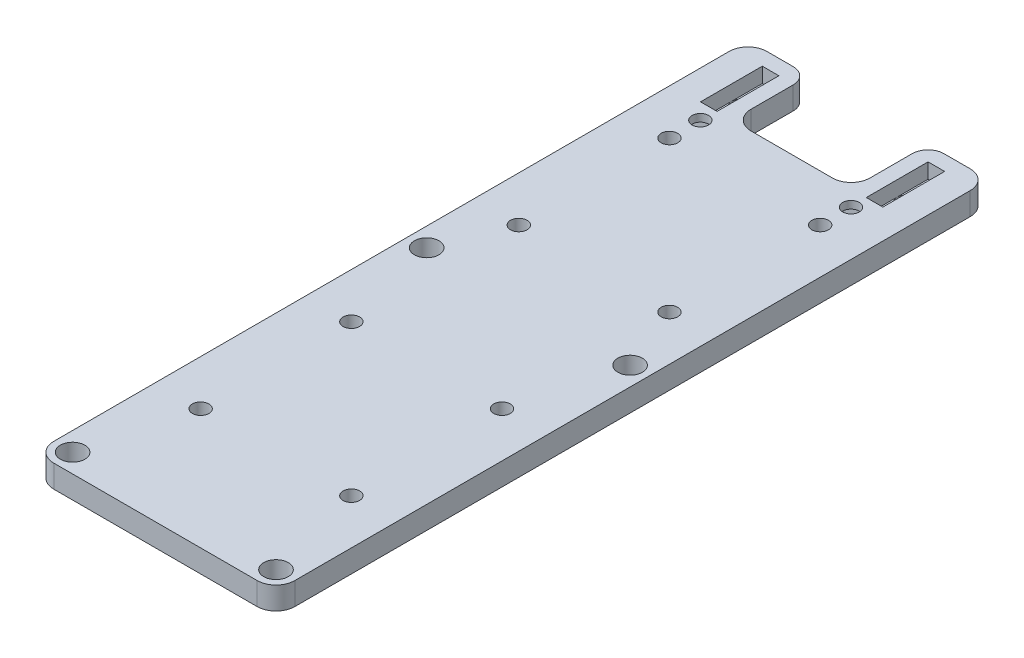
SolidWorks part; units mm, degrees
ref_plane "Front Plane" through (0, 0, 0) normal (0, 0, 1) x (1, 0, 0)
ref_plane "Top Plane" through (0, 0, 0) normal (0, 1, 0) x (1, 0, 0)
ref_plane "Right Plane" through (0, 0, 0) normal (1, 0, 0) x (0, 0, -1)
sketch "Sketch1" plane through (0, 0, 0) normal (0, 1, 0) x (1, 0, 0)
  line L0 (0, 42.225) -> (0, -42.225) construction
  line L1 (16, 42.225) -> (-16, 42.225)
  line L2 (16, 42.225) -> (16, -42.225)
  line L3 (16, -42.225) -> (-16, -42.225)
  line L4 (-16, 42.225) -> (-16, -42.225)
  line L5 (16, 42.225) -> (-16, -42.225) construction
  line L6 (16, -42.225) -> (-16, 42.225) construction
  line L12 (-12.1, 50.425) -> (-12.1, 52.425) construction
  line L17 (-11, 52.425) -> (-11, 42.225) construction
  line L18 (-7.9, 42.225) -> (-14.1, 42.225)
  line L20 (-10, 36) -> (10, 36)
  line L21 (-10, 36) -> (-10, 16)
  line L22 (-10, 16) -> (10, 16)
  line L23 (10, 36) -> (10, 16)
  line L24 (-10, 36) -> (10, 16) construction
  line L25 (-10, 16) -> (10, 36) construction
  line L26 (-14.5, 10.775) -> (14.5, 10.775)
  line L27 (-14.5, 10.775) -> (-14.5, 41.225)
  line L28 (-14.5, 41.225) -> (14.5, 41.225)
  line L29 (14.5, 10.775) -> (14.5, 41.225)
  line L30 (-14.5, 10.775) -> (14.5, 41.225) construction
  line L31 (-14.5, 41.225) -> (14.5, 10.775) construction
  line L32 (-10, -6.225) -> (10, -6.225)
  line L33 (-10, -6.225) -> (-10, -26.225)
  line L34 (-10, -26.225) -> (10, -26.225)
  line L35 (10, -6.225) -> (10, -26.225)
  line L36 (-10, -6.225) -> (10, -26.225) construction
  line L37 (-10, -26.225) -> (10, -6.225) construction
  line L38 (-15.75, -36.225) -> (15.75, -36.225)
  line L39 (-15.75, -36.225) -> (-15.75, 3.775)
  line L40 (-15.75, 3.775) -> (15.75, 3.775)
  line L41 (15.75, -36.225) -> (15.75, 3.775)
  line L42 (-15.75, -36.225) -> (15.75, 3.775) construction
  line L43 (-15.75, 3.775) -> (15.75, -36.225) construction
  line L48 (-7.9, 42.225) -> (-7.9, 52.425)
  line L49 (-7.9, 52.425) -> (-14.1, 52.425)
  line L59 (-14.1, 42.225) -> (-14.1, 52.425)
  line L63 (-12.1, 50.425) -> (-9.9, 50.425)
  line L64 (-12.1, 50.425) -> (-12.1, 42.225)
  line L65 (-12.1, 42.225) -> (-9.9, 42.225)
  line L66 (-9.9, 50.425) -> (-9.9, 42.225)
  line L67 (-12.1, 50.425) -> (-9.9, 42.225) construction
  line L68 (-12.1, 42.225) -> (-9.9, 50.425) construction
  line L69 (-12.1, 50.425) -> (-14.1, 50.425) construction
  line L74 (7.9, 42.225) -> (14.1, 42.225)
  line L75 (14.1, 42.225) -> (14.1, 52.425)
  line L76 (7.9, 52.425) -> (14.1, 52.425)
  line L77 (7.9, 42.225) -> (7.9, 52.425)
  line L78 (12.1, 50.425) -> (9.9, 50.425)
  line L79 (12.1, 50.425) -> (12.1, 42.225)
  line L80 (12.1, 42.225) -> (9.9, 42.225)
  line L81 (9.9, 50.425) -> (9.9, 42.225)
  line L82 (-14.5, 10.775) -> (-14.5, 3.775) construction
  line L83 (-14.5, 7.275) -> (16, 7.275) construction
  line L89 (-13.5, -37.225) -> (-16, -37.225) construction
  line L94 (-14.1, 52.425) -> (-16, 52.425)
  line L95 (-14.1, 52.425) -> (-14.1, 42.225)
  line L96 (-14.1, 42.225) -> (-16, 42.225)
  line L97 (-16, 52.425) -> (-16, 42.225)
  line L98 (14.1, 52.425) -> (16, 52.425)
  line L99 (14.1, 52.425) -> (14.1, 42.225)
  line L100 (14.1, 42.225) -> (16, 42.225)
  line L101 (16, 52.425) -> (16, 42.225)
  circle A3 centre (-10, 36) radius 1.1
  circle A4 centre (10, 36) radius 1.1
  circle A5 centre (10, 16) radius 1.1
  circle A6 centre (-10, 16) radius 1.1
  circle A7 centre (-10, -6.225) radius 1.1
  circle A8 centre (10, -6.225) radius 1.1
  circle A9 centre (10, -26.225) radius 1.1
  circle A10 centre (-10, -26.225) radius 1.1
  circle A37 centre (-13.5, 7.275) radius 2.5
  circle A38 centre (-13.5, 7.275) radius 1.625
  circle A39 centre (13.5, 7.275) radius 1.625
  circle A40 centre (-13.5, -39.725) radius 2.5
  circle A41 centre (-13.5, -39.725) radius 1.625
  circle A42 centre (13.5, -39.725) radius 1.625
  point P0 (0, 0)
  point P8 (0, 0)
  point P16 (0, 26)
  point P26 (0, 26)
  point P31 (0, -16.225)
  point P36 (0, -16.225)
  point P61 (-11, 46.325)
  dimension "D3" = 2
  dimension "D17" = 2.2
  dimension "D22" = 5
  dimension "D23" = 3.25
  dimension "D8" = 32
  dimension "D9" = 22
  dimension "D10" = 20
  dimension "D11" = 29
  dimension "D12" = 30.45
  dimension "D13" = 40
  dimension "D14" = 31.5
  dimension "D15" = 1
  dimension "D16" = 7
  dimension "D18" = 2.2
  dimension "D20" = 8.2
  dimension "D24" = 1
extrude "Boss-Extrude1" add sketch "Sketch1" along normal blind 2 contours L63 L66 L1 L48 L49 L59 L18 L64 | L81 L78 L79 L1 L75 L76 L77 | L94 L97 L1 L59 | L101 L98 L75 L1 | L1 L4 L3 L2 | A4 | A3 | A7 | A8 | A9 | A10 | A5 | A6 | A39 | A38 | A41 | A42 region at (15.05, 0, -47.325) region at (13.1, 0, -42.3444) region at (-8.9, 0, -42.3444) region at (-15.05, 0, -47.325)
sketch "Sketch2" plane through (0, 0, 0) normal (0, -1, 0) x (1, 0, 0)
  line L0 (-12.1, -42.225) -> (-9.9, -50.425) construction
  line L1 (12.1, -42.225) -> (9.9, -50.425) construction
  line L4 (12.1, -42.225) -> (9.9, -42.225)
  line L5 (12.1, -50.425) -> (12.1, -42.225)
  line L6 (9.9, -50.425) -> (12.1, -50.425)
  line L7 (9.9, -42.225) -> (9.9, -50.425)
  line L8 (12.1, -42.225) -> (9.9, -42.225)
  line L9 (12.1, -50.425) -> (12.1, -42.225)
  line L10 (9.9, -50.425) -> (12.1, -50.425)
  line L11 (9.9, -42.225) -> (9.9, -50.425)
  line L12 (-9.9, -42.225) -> (-12.1, -42.225)
  line L13 (-9.9, -50.425) -> (-9.9, -42.225)
  line L14 (-12.1, -50.425) -> (-9.9, -50.425)
  line L15 (-12.1, -42.225) -> (-12.1, -50.425)
  line L16 (-9.9, -42.225) -> (-12.1, -42.225)
  line L17 (-9.9, -50.425) -> (-9.9, -42.225)
  line L18 (-12.1, -50.425) -> (-9.9, -50.425)
  line L19 (-12.1, -42.225) -> (-12.1, -50.425)
  circle A0 centre (-11, -46.325) radius 1.1
  circle A1 centre (11, -46.325) radius 1.1
  dimension "D1" = 0
  dimension "D2" = 0
extrude "Boss-Extrude2" add sketch "Sketch2" against normal offset from surface (1 mm away) 1 contours A0 L19 | A0 L17 | A1 L9 | A1 L11 region at (11, 0, -43.8523) region at (11, 0, -48.7977) region at (-11, 0, -43.8523) region at (-11, 0, -48.7977) up to face at (11, 2, -46.325)
fillet "Fillet1" radius 2.5 6 edges at (7.9, 1, -42.225) (-7.9, 1, -42.225) (-16, 1, -52.425) (16, 1, -52.425) (-16, 1, 42.225) (16, 1, 42.225)
fillet "Fillet2" radius 2.1 2 edges at (-7.9, 1, -52.425) (7.9, 1, -52.425)
sketch "Sketch3" plane through (0, 2, 0) normal (0, 1, 0) x (1, 0, 0)
  line L6 (12.1, 42.225) -> (12.1, 50.425)
  line L7 (9.9, 42.225) -> (12.1, 42.225)
  line L8 (-10, 52.425) -> (-13.5, 52.425)
  line L9 (-16, 49.925) -> (-16, -39.725)
  line L10 (-13.5, -42.225) -> (13.5, -42.225)
  line L11 (16, -39.725) -> (16, 49.925)
  line L12 (13.5, 52.425) -> (10, 52.425)
  line L13 (7.9, 50.325) -> (7.9, 44.725)
  line L14 (5.4, 42.225) -> (-5.4, 42.225)
  line L15 (-7.9, 44.725) -> (-7.9, 50.325)
  line L16 (-10, 52.425) -> (-13.5, 52.425)
  line L17 (-16, 49.925) -> (-16, -39.725)
  line L18 (-13.5, -42.225) -> (13.5, -42.225)
  line L19 (16, -39.725) -> (16, 49.925)
  line L20 (13.5, 52.425) -> (10, 52.425)
  line L21 (7.9, 50.325) -> (7.9, 44.725)
  line L22 (5.4, 42.225) -> (-5.4, 42.225)
  line L23 (-7.9, 44.725) -> (-7.9, 50.325)
  line L24 (9.9, 50.425) -> (9.9, 42.225)
  line L25 (12.1, 50.425) -> (9.9, 50.425)
  line L26 (12.1, 42.225) -> (12.1, 50.425)
  line L27 (9.9, 42.225) -> (12.1, 42.225)
  line L28 (9.9, 50.425) -> (9.9, 42.225)
  line L29 (12.1, 50.425) -> (9.9, 50.425)
  line L30 (-9.9, 42.225) -> (-9.9, 50.425)
  line L31 (-12.1, 42.225) -> (-9.9, 42.225)
  line L32 (-12.1, 50.425) -> (-12.1, 42.225)
  line L33 (-9.9, 50.425) -> (-12.1, 50.425)
  line L34 (-9.9, 42.225) -> (-9.9, 50.425)
  line L35 (-12.1, 42.225) -> (-9.9, 42.225)
  line L36 (-12.1, 50.425) -> (-12.1, 42.225)
  line L37 (-9.9, 50.425) -> (-12.1, 50.425)
  circle A0 centre (13.5, -39.725) radius 1.625 construction
  circle A1 centre (-13.5, -39.725) radius 1.625 construction
  circle A2 centre (-13.5, 7.275) radius 1.625 construction
  circle A3 centre (-10, -6.225) radius 1.1 construction
  circle A4 centre (-10, -26.225) radius 1.1 construction
  circle A5 centre (10, -26.225) radius 1.1 construction
  circle A6 centre (10, -6.225) radius 1.1 construction
  circle A7 centre (13.5, 7.275) radius 1.625 construction
  arc A8 (-13.5, 52.425) -> (-16, 49.925) centre (-13.5, 49.925) ccw
  arc A9 (-16, -39.725) -> (-13.5, -42.225) centre (-13.5, -39.725) ccw
  arc A10 (13.5, -42.225) -> (16, -39.725) centre (13.5, -39.725) ccw
  arc A11 (16, 49.925) -> (13.5, 52.425) centre (13.5, 49.925) ccw
  arc A12 (-7.9, 50.325) -> (-10, 52.425) centre (-10, 50.325) ccw
  arc A13 (5.4, 42.225) -> (7.9, 44.725) centre (5.4, 44.725) ccw
  arc A14 (-7.9, 44.725) -> (-5.4, 42.225) centre (-5.4, 44.725) ccw
  arc A15 (-7.9, 50.325) -> (-10, 52.425) centre (-10, 50.325) ccw
  arc A16 (-13.5, 52.425) -> (-16, 49.925) centre (-13.5, 49.925) ccw
  arc A17 (-16, -39.725) -> (-13.5, -42.225) centre (-13.5, -39.725) ccw
  arc A18 (13.5, -42.225) -> (16, -39.725) centre (13.5, -39.725) ccw
  arc A19 (16, 49.925) -> (13.5, 52.425) centre (13.5, 49.925) ccw
  arc A21 (5.4, 42.225) -> (7.9, 44.725) centre (5.4, 44.725) ccw
  arc A22 (-7.9, 44.725) -> (-5.4, 42.225) centre (-5.4, 44.725) ccw
  circle A24 centre (-10, 16) radius 1.1 construction
  circle A25 centre (-10, 36) radius 1.1 construction
  circle A26 centre (10, 36) radius 1.1 construction
  circle A27 centre (10, 16) radius 1.1 construction
  circle A28 centre (10, 16) radius 1.1
  circle A29 centre (10, 36) radius 1.1
  circle A30 centre (-10, 36) radius 1.1
  circle A31 centre (-10, 16) radius 1.1
  circle A32 centre (13.5, 7.275) radius 1.625
  circle A33 centre (10, -6.225) radius 1.1
  circle A34 centre (10, -26.225) radius 1.1
  circle A35 centre (-10, -26.225) radius 1.1
  circle A36 centre (-10, -6.225) radius 1.1
  circle A37 centre (13.5, -39.725) radius 1.625
  circle A38 centre (-13.5, -39.725) radius 1.625
  circle A39 centre (-13.5, 7.275) radius 1.625
  arc A48 (10, 52.425) -> (7.9, 50.325) centre (10, 50.325) ccw
  arc A49 (10, 52.425) -> (7.9, 50.325) centre (10, 50.325) ccw
  dimension "D1" = 0
  dimension "D2" = 0
  dimension "D3" = 0
extrude "Boss-Extrude3" add sketch "Sketch3" along normal blind 1
sketch "Sketch4" plane through (0, 0, 0) normal (0, -1, 0) x (1, 0, 0)
  line L0 (0, 13.9568) -> (0, -8.6953) construction
  line L1 (-14.1, -38.5) -> (-5.9, -38.5)
  line L2 (-14.1, -38.5) -> (-14.1, -41.7)
  line L3 (-14.1, -41.7) -> (-5.9, -41.7)
  line L4 (-5.9, -38.5) -> (-5.9, -41.7)
  line L5 (-10, -38.5) -> (-10, -41.7) construction
  line L7 (14.1, -38.5) -> (5.9, -38.5)
  line L8 (14.1, -38.5) -> (14.1, -41.7)
  line L9 (14.1, -41.7) -> (5.9, -41.7)
  line L10 (5.9, -38.5) -> (5.9, -41.7)
  line L11 (-14.1, -38.5) -> (-10.9, -41.7) construction
  line L12 (-14.1, -40.1) -> (-5.9, -40.1) construction
  circle A0 centre (-10, -36) radius 2
  circle A1 centre (-13.3929, -39.2071) radius 1
  circle A2 centre (-13.3929, -40.9929) radius 1
  circle A3 centre (-6.6071, -39.2071) radius 1
  circle A4 centre (-6.6071, -40.9929) radius 1
  circle A5 centre (6.6071, -40.9929) radius 1
  circle A6 centre (6.6071, -39.2071) radius 1
  circle A7 centre (13.3929, -39.2071) radius 1
  circle A8 centre (13.3929, -40.9929) radius 1
  point P9 (-10, -38)
  dimension "D5" = 4
  dimension "D7" = 2
  dimension "D1" = 8.2
  dimension "D2" = 3.2
  dimension "D3" = 10
  dimension "D4" = 0.5
  dimension "D6" = 45
extrude "Cut-Extrude1" cut sketch "Sketch4" against normal offset from surface (2 mm away) 1 contours A2 L2 | A2 L3 | L2 A1 | L1 A1 | A3 L4 | A3 L1 | L4 A4 | L3 A4 | A5 L9 | A5 L10 | L10 A6 | L7 A6 | A7 L7 | A7 L8 | L8 A8 | L9 A8 | L3 L4 L1 L2 | L9 L10 L7 L8 region at (-13.3929, 0, -38.3812) region at (-14.2188, 0, -39.2071) region at (-6.6071, 0, -38.3812) region at (-14.2188, 0, -40.9929) region at (-5.7812, 0, -39.2071) region at (-13.3929, 0, -41.8188) region at (-6.6071, 0, -41.8188) region at (-5.7812, 0, -40.9929) region at (14.2188, 0, -39.2071) region at (13.3929, 0, -38.3812) region at (6.6071, 0, -38.3812) region at (14.2188, 0, -40.9929) region at (5.7812, 0, -39.2071) region at (13.3929, 0, -41.8188) region at (6.6071, 0, -41.8188) region at (5.7812, 0, -40.9929) up to face at (-13.5, 3, 41.35)
sketch "Sketch5" plane through (0, 2, 0) normal (0, -1, 0) x (1, 0, 0)
  line L0 (-10, -38.5) -> (-10, -41.7) construction
  line L1 (-12.6858, -38.5) -> (-7.3142, -38.5) construction
  line L2 (-12.6858, -41.7) -> (-7.3142, -41.7) construction
  line L3 (0, 5.9884) -> (0, -5.6723) construction
  circle A0 centre (-10, -40.1) radius 1.1
  circle A1 centre (10, -40.1) radius 1.1
  dimension "D1" = 2.2
extrude "Cut-Extrude2" cut sketch "Sketch5" against normal up to next
